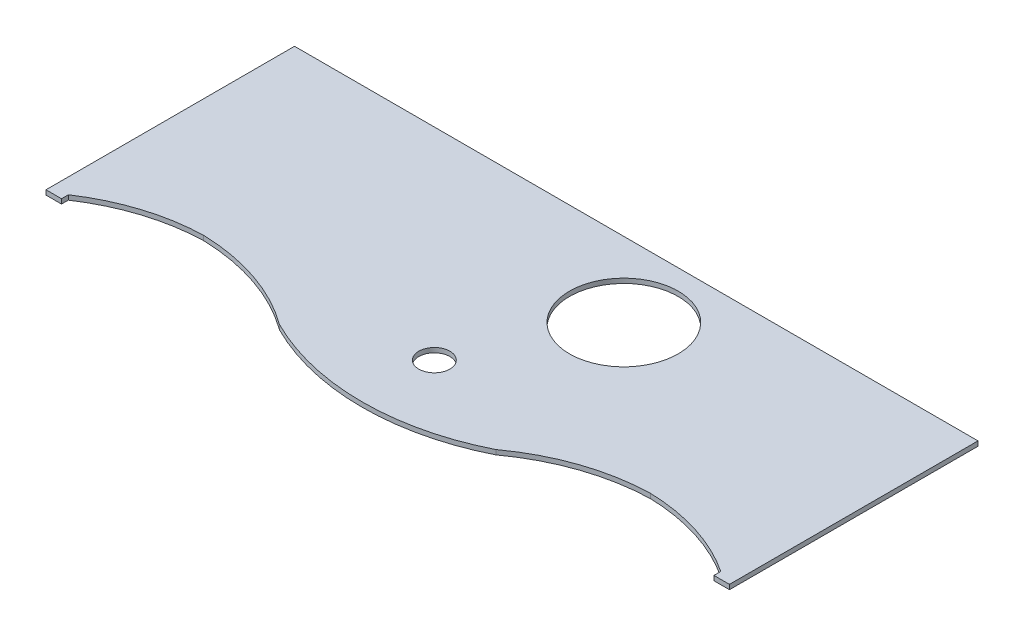
SolidWorks part; units mm, degrees
ref_plane "Front Plane" through (0, 0, 0) normal (0, 0, 1) x (1, 0, 0)
ref_plane "Top Plane" through (0, 0, 0) normal (0, 1, 0) x (1, 0, 0)
ref_plane "Right Plane" through (0, 0, 0) normal (1, 0, 0) x (0, 0, -1)
ref_plane "Plane1" through (0, 22.5, 0) normal (0, 1, 0) x (1, 0, 0)
ref_plane "Plane2" through (0, 24, 0) normal (0, 1, 0) x (1, 0, 0)
sketch "Sketch2" plane through (0, 22.5, 0) normal (0, 1, 0) x (1, 0, 0)
  line L0 (0, -100) -> (0, 70) construction
  line L7 (71.9147, -28) -> (71.9147, -17.3273) construction
  line L8 (-110, 50) -> (110, 50)
  line L9 (-105, -27.799) -> (-105, -30.0025)
  line L10 (-105, -30.0025) -> (-110, -30)
  line L11 (-110, -30) -> (-110, 50)
  line L12 (110, 50) -> (110, -30)
  line L13 (110, -30) -> (105, -30.0025)
  line L14 (105, -30.0025) -> (105, -27.799)
  line L15 (-34.8399, -30) -> (34.8399, -30) construction
  arc A0 (-105, -27.799) -> (-71.9147, -17.3273) centre (-70.2175, -80.192) cw
  arc A1 (-71.9147, -17.3273) -> (-105, -27.799) centre (-70.2175, -80.192) ccw construction
  arc A2 (-71.9147, -17.3273) -> (-34.8399, -30) centre (-73.6989, -83.1159) cw
  arc A3 (-34.8399, -30) -> (-71.9147, -17.3273) centre (-73.6989, -83.1159) ccw construction
  arc A6 (34.8399, -30) -> (71.9147, -17.3273) centre (73.6989, -83.1159) cw
  arc A7 (71.9147, -17.3273) -> (34.8399, -30) centre (73.6989, -83.1159) ccw construction
  arc A8 (71.9147, -17.3273) -> (105, -27.799) centre (70.2175, -80.192) cw
  arc A9 (105, -27.799) -> (71.9147, -17.3273) centre (70.2175, -80.192) ccw construction
  arc A11 (105, -27.799) -> (71.9147, -17.3273) centre (70.2175, -80.192) ccw construction
  circle A12 centre (20, 26) radius 17.5
  circle A13 centre (20, 26) radius 17.5 construction
  circle A14 centre (0, -15) radius 5
  circle A15 centre (0, -15) radius 5 construction
  arc A16 (-34.8399, -30) -> (34.8399, -30) centre (0, 39.341) ccw
  arc A17 (-34.8399, -30) -> (34.8399, -30) centre (0, 39.341) ccw construction
  point P0 (0, 10.0408)
extrude "Boss-Extrude2" add sketch "Sketch2" along normal up to surface (1.5 mm away) up to plane "Plane2"
